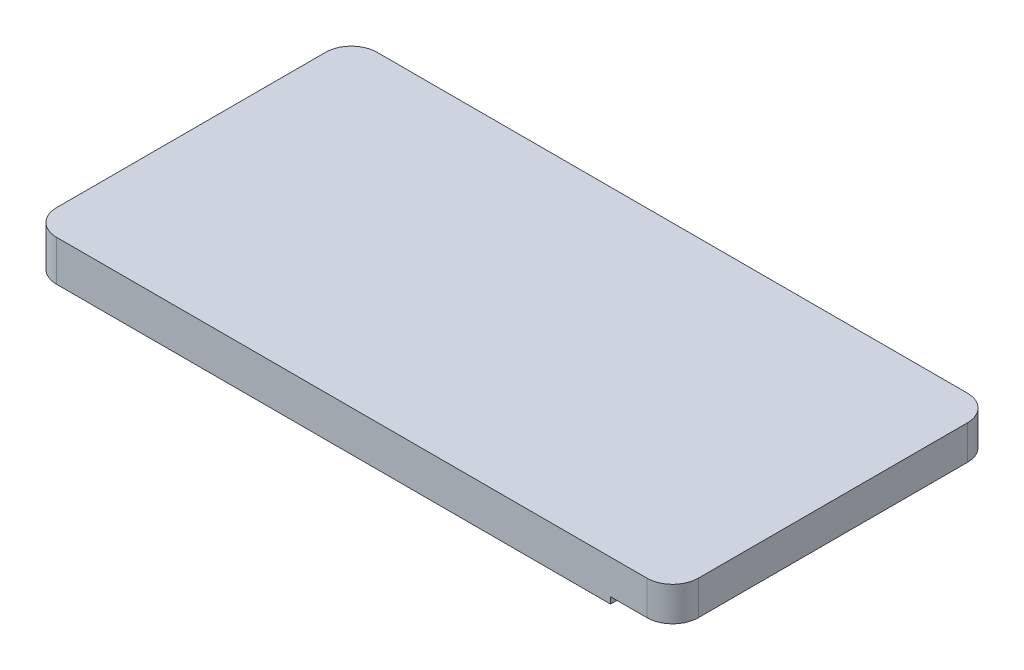
SolidWorks part; units mm, degrees
ref_plane "前视基准面" through (0, 0, 0) normal (0, 0, 1) x (1, 0, 0)
ref_plane "上视基准面" through (0, 0, 0) normal (0, 1, 0) x (1, 0, 0)
ref_plane "右视基准面" through (0, 0, 0) normal (1, 0, 0) x (0, 0, -1)
sketch "草图1" plane through (0, 0, 0) normal (0, 1, 0) x (1, 0, 0)
  line L1 (6, 0) -> (143.8, 0)
  line L2 (0, -6) -> (0, -68.8)
  line L3 (6, -74.8) -> (143.8, -74.8)
  line L4 (149.8, -6) -> (149.8, -68.8)
  arc A0 (143.8, 0) -> (149.8, -6) centre (143.8, -6) cw
  arc A1 (143.8, -74.8) -> (149.8, -68.8) centre (143.8, -68.8) ccw
  arc A2 (0, -68.8) -> (6, -74.8) centre (6, -68.8) ccw
  arc A3 (6, 0) -> (0, -6) centre (6, -6) ccw
  point P7 (149.8, 0)
  point P12 (0, -74.8)
  point P15 (0, 0)
  dimension "D3" = 6
  dimension "D1" = 74.8
  dimension "D2" = 149.8
extrude "凸台-拉伸1" add sketch "草图1" along normal blind 9.5
sketch "草图2" plane through (0, 0, 0) normal (0, -1, 0) x (-1, 0, 0)
  line L0 (-122.6, -55.35) -> (-108.9, -55.35)
  line L1 (-122.6, -69.85) -> (-108.9, -69.85)
  line L2 (-122.6, -69.85) -> (-122.6, -63.95)
  line L3 (-122.6, -63.95) -> (-108.9, -63.95)
  line L4 (-108.9, -69.85) -> (-108.9, -63.95)
  line L5 (-135.3, -1.25) -> (-35.3, -1.25) construction
  line L6 (-135.3, -1.25) -> (-135.3, -73.55) construction
  line L7 (-135.3, -73.55) -> (-35.3, -73.55) construction
  line L8 (-35.3, -1.25) -> (-35.3, -73.55) construction
  line L9 (-108.9, -61.25) -> (-108.9, -55.35)
  line L10 (-122.6, -61.25) -> (-108.9, -61.25)
  line L11 (-122.6, -61.25) -> (-122.6, -55.35)
  line L12 (-122.6, -46.75) -> (-108.9, -46.75)
  line L13 (-108.9, -52.65) -> (-108.9, -46.75)
  line L14 (-122.6, -52.65) -> (-108.9, -52.65)
  line L15 (-122.6, -52.65) -> (-122.6, -46.75)
  line L16 (-122.6, -38.15) -> (-108.9, -38.15)
  line L17 (-108.9, -44.05) -> (-108.9, -38.15)
  line L18 (-122.6, -44.05) -> (-108.9, -44.05)
  line L19 (-122.6, -44.05) -> (-122.6, -38.15)
  line L20 (0, -6) -> (0, -68.8) construction
  line L21 (-35.3, -73.55) -> (-0.8, -73.55) construction
  line L22 (-120.25, -26.65) -> (-111.25, -26.65)
  line L23 (-120.25, -26.65) -> (-120.25, -33.15)
  line L24 (-120.25, -33.15) -> (-111.25, -33.15)
  line L25 (-111.25, -26.65) -> (-111.25, -33.15)
  line L26 (-85.8, -48.75) -> (-81.1, -48.75)
  line L27 (-85.8, -48.75) -> (-85.8, -58.15)
  line L28 (-85.8, -58.15) -> (-81.1, -58.15)
  line L29 (-81.1, -48.75) -> (-81.1, -58.15)
  line L30 (-71.5, -48.65) -> (-68.2, -48.65)
  line L31 (-71.5, -48.65) -> (-71.5, -57.55)
  line L32 (-71.5, -57.55) -> (-68.2, -57.55)
  line L33 (-68.2, -48.65) -> (-68.2, -57.55)
  line L34 (-43.1, -45.05) -> (-38.6, -45.05)
  line L35 (-43.1, -45.05) -> (-43.1, -59.05)
  line L36 (-43.1, -59.05) -> (-38.6, -59.05)
  line L37 (-38.6, -45.05) -> (-38.6, -59.05)
  line L38 (-45.3, -61.55) -> (-40.8, -61.55)
  line L39 (-45.3, -61.55) -> (-45.3, -66.05)
  line L40 (-45.3, -66.05) -> (-40.8, -66.05)
  line L41 (-40.8, -61.55) -> (-40.8, -66.05)
  line L42 (-0.8, -73.55) -> (-0.8, -1.25) construction
  line L43 (-0.8, -1.25) -> (-35.3, -1.25) construction
  line L44 (-149.8, -6) -> (-149.8, -68.8) construction
  line L45 (-30.8, -34.65) -> (-27.3, -34.65)
  line L46 (-30.8, -34.65) -> (-30.8, -40.15)
  line L47 (-30.8, -40.15) -> (-27.3, -40.15)
  line L48 (-27.3, -34.65) -> (-27.3, -40.15)
  line L50 (-80.067, -46.6) -> (-74.167, -46.6)
  line L51 (-80.067, -46.6) -> (-80.067, -59.6)
  line L52 (-80.067, -59.6) -> (-74.167, -59.6)
  line L53 (-74.167, -46.6) -> (-74.167, -59.6)
  circle A0 centre (-103.2, -9.35) radius 1.65
  circle A1 centre (-103.2, -64.25) radius 1.65
  circle A2 centre (-59.2, -64.25) radius 1.65
  circle A3 centre (-59.2, -9.35) radius 1.65
  circle A4 centre (-130.8, -5.6) radius 1.25
  circle A5 centre (-131.1, -55.65) radius 1.25
  circle A6 centre (-47.7, -4.85) radius 1.25
  circle A7 centre (-48.1, -68.75) radius 1.25
  circle A8 centre (-22.8, -70.3) radius 1.25
  circle A9 centre (-5.05, -71.05) radius 1.25
  circle A10 centre (-5.05, -3.25) radius 1.25
  circle A11 centre (-19, -37.4) radius 3.6
  point P22 (0, -37.4)
  point P23 (-135.3, -37.4)
  point P28 (-115.75, -33.15)
  point P29 (-115.75, -38.15)
  point P30 (-111.25, -29.9)
  point P31 (-108.9, -41.1)
  point P79 (-0.8, -37.4)
  point P81 (-27.3, -37.4)
  point P86 (-74.167, -53.1)
  point P87 (-71.5, -53.1)
  dimension "D21" = 3.3
  dimension "D34" = 2.5
  dimension "D53" = 7.2
  dimension "D1" = 13.7
  dimension "D2" = 5.9
  dimension "D3" = 72.3
  dimension "D4" = 3.7
  dimension "D5" = 12.7
  dimension "D7" = 14.5
  dimension "D8" = 100
  dimension "D9" = 2.7
  dimension "D10" = 9
  dimension "D11" = 6.5
  dimension "D12" = 11.2
  dimension "D13" = 15.4
  dimension "D14" = 9.4
  dimension "D15" = 4.7
  dimension "D16" = 23.1
  dimension "D17" = 3.3
  dimension "D18" = 8.9
  dimension "D19" = 16
  dimension "D20" = 37.4
  dimension "D22" = 8.1
  dimension "D23" = 32.1
  dimension "D24" = 44
  dimension "D25" = 9.3
  dimension "D26" = 14
  dimension "D27" = 4.5
  dimension "D28" = 4.5
  dimension "D29" = 4.5
  dimension "D30" = 3.3
  dimension "D31" = 5.5
  dimension "D32" = 7.5
  dimension "D33" = 14.5
  dimension "D35" = 34.5
  dimension "D36" = 2
  dimension "D37" = 4.25
  dimension "D38" = 2.5
  dimension "D39" = 3.25
  dimension "D40" = 22
  dimension "D41" = 4.8
  dimension "D42" = 12.8
  dimension "D43" = 3.6
  dimension "D44" = 12.4
  dimension "D45" = 4.35
  dimension "D46" = 4.5
  dimension "D47" = 4.2
  dimension "D48" = 17.9
  dimension "D49" = 18.2
  dimension "D50" = 3.5
  dimension "D51" = 5.5
  dimension "D52" = 8.3
  dimension "D54" = 5.9
  dimension "D55" = 13
  dimension "D6" = 4
extrude "凸台-拉伸5" add sketch "草图2<5>" along normal blind 1.5 contours L38 L41 L40 L39 | L35 L36 L37 L34
sketch "草图2<5>" plane through (0, 0, 0) normal (0, -1, 0) x (-1, 0, 0) same geometry as "草图2"
extrude "凸台-拉伸6" add sketch "草图2<6>" along normal blind 1 contours A4 | A5 | A6 | A7 | A8 | A9 | A10
sketch "草图2<6>" plane through (0, 0, 0) normal (0, -1, 0) x (-1, 0, 0) same geometry as "草图2"
extrude "切除-拉伸1" cut sketch "草图2<7>" against normal blind 4 contours A0 | A3 | A1 | A2
sketch "草图2<7>" plane through (0, 0, 0) normal (0, -1, 0) x (-1, 0, 0) same geometry as "草图2"
sketch "草图3" plane through (0, 0, 0) normal (0, 1, 0) x (1, 0, 0)
  line L0 (135.3, -1.25) -> (135.3, -73.55) construction
  line L1 (149.8, 0) -> (135.3, 0)
  line L2 (149.8, 0) -> (149.8, -74.8)
  line L3 (149.8, -74.8) -> (135.3, -74.8)
  line L4 (135.3, 0) -> (135.3, -74.8)
  line L5 (6, -74.8) -> (143.8, -74.8) construction
extrude "切除-拉伸2" cut sketch "草图3" along normal blind 1.5
extrude "凸台-拉伸7" add sketch "草图2" along normal blind 5 contours A11 | L47 L48 L45 L46
